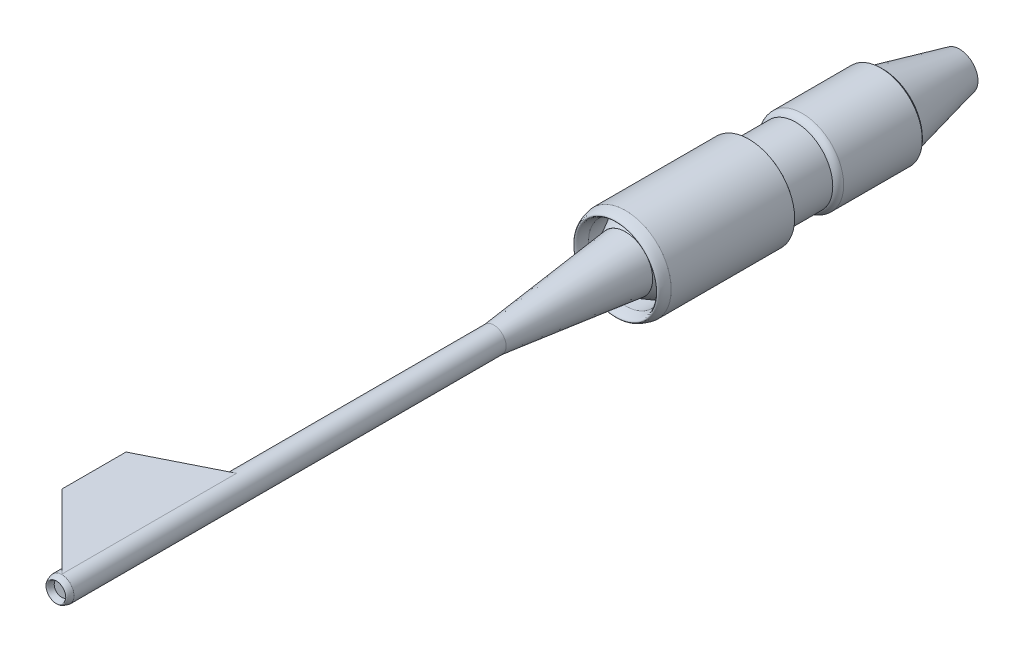
SolidWorks part; units mm, degrees
ref_plane "Front Plane" through (0, 0, 0) normal (0, 0, 1) x (1, 0, 0)
ref_plane "Top Plane" through (0, 0, 0) normal (0, 1, 0) x (1, 0, 0)
ref_plane "Right Plane" through (0, 0, 0) normal (1, 0, 0) x (0, 0, -1)
sketch "Sketch1" plane through (0, 0, 0) normal (0, 0, 1) x (1, 0, 0)
  circle A0 centre (0, 0) radius 416.25
  circle A1 centre (0, 0) radius 337.5
extrude "Boss-Extrude1" add sketch "Sketch1" against normal blind 1125
sketch "Sketch2" plane through (0, 0, 0) normal (1, 0, 0) x (0, 0, -1)
  line L0 (0, 416.25) -> (0, 337.5) construction
  line L1 (0, 337.5) -> (0, 376.875) construction
  line L2 (0, 376.875) -> (-90, 376.875) construction
  line L3 (0, 416.25) -> (0, 337.5)
  line L4 (0, 0) -> (98.8797, 0) construction
  spline S0 degree 2 poles (0, 337.5) (-180, 376.875) (0, 416.25) knots 0 0 0 1 1 1
revolve "Revolve1" add sketch "Sketch2" angle 360 about L4
ref_plane "Plane1" through (0, 0, 0) normal (0, 0, 1) x (1, 0, 0)
sketch "Sketch3" plane through (0, 0, 0) normal (0, 0, 1) x (1, 0, 0)
  circle A0 centre (0, 0) radius 247.5
sketch "Sketch4" plane through (0, 0, 0) normal (0, 1, 0) x (1, 0, 0)
  line L0 (0, 0) -> (0, -1200)
  line L1 (0, -1200) -> (112.5, -1200)
  line L2 (0, 0) -> (247.5, 0)
  line L3 (-247.5, 0) -> (247.5, 0) construction
  line L4 (-457.875, 0) -> (457.875, 0) construction
  line L5 (247.5, 0) -> (112.5, -1200)
revolve "Revolve2" add sketch "Sketch4" angle 360 about L0
sketch "Sketch5" plane through (0, 0, 1200) normal (0, 0, 1) x (1, 0, 0)
  circle A0 centre (0, 0) radius 112.5
extrude "Boss-Extrude2" add sketch "Sketch5" along normal blind 3937.5
sketch "Sketch14" plane through (0, 0, 0) normal (1, 0, 0) x (0, 0, -1)
  line L0 (-5137.5, 112.5) -> (-5137.5, 67.5)
  line L1 (-5137.5, 112.5) -> (-5137.5, -112.5) construction
  line L2 (-5137.5, 67.5) -> (-5137.5, 90)
  line L3 (-5137.5, 90) -> (-5187.5, 90) construction
  line L4 (-5137.5, 0) -> (-5198.2274, 0) construction
  line L5 (-5137.5, 112.5) -> (-5137.5, -112.5) construction
  spline S0 degree 2 poles (-5137.5, 67.5) (-5237.5, 90) (-5137.5, 112.5) knots 0 0 0 1 1 1
  dimension "D1" = 50
  dimension "D2" = 67.5
  dimension "D3" = 90
revolve "Revolve4" add sketch "Sketch14" angle 360 about L4 region at (0, 90, 5157.5)
sketch "Sketch15" plane through (0, 0, -1125) normal (0, 0, -1) x (-1, 0, 0)
  circle A0 centre (0, 0) radius 337.5
extrude "Boss-Extrude5" add sketch "Sketch15" along normal blind 486 separate body
sketch "Sketch16" plane through (0, 0, -1611) normal (0, 0, -1) x (-1, 0, 0)
  line L0 (0, 337.5) -> (0, 416.25) construction
  line L1 (0, 376.875) -> (79.8334, 376.875) construction
  circle A0 centre (0, 0) radius 337.5 construction
  circle A1 centre (0, 0) radius 337.5 construction
  circle A2 centre (0, 0) radius 416.25 construction
  circle A4 centre (0, 0) radius 376.875
extrude "Boss-Extrude6" add sketch "Sketch16" along normal blind 716
sketch "Sketch17" plane through (0, 0, 0) normal (1, 0, 0) x (0, 0, -1)
  line L0 (2327, 0) -> (3043, 0)
  line L1 (2327, -376.875) -> (2327, 376.875) construction
  line L2 (3043, 0) -> (3043, 168.75)
  line L3 (1611, 337.5) -> (2327, 337.5) construction
  line L4 (2327, 0) -> (2327, 337.5)
  line L5 (2327, 337.5) -> (3043, 168.75)
revolve "Revolve5" add sketch "Sketch17" angle 360 about L0
sketch "Sketch18" plane through (0, 0, 0) normal (1, 0, 0) x (0, 0, -1)
  line L0 (0, 247.5) -> (306.6324, 416.25)
  line L1 (1125, 416.25) -> (0, 416.25) construction
  line L2 (0, 247.5) -> (306.6324, 247.5)
  line L3 (306.6324, 247.5) -> (306.6324, 416.25)
  line L4 (0, 0) -> (306.6324, 0) construction
revolve "Revolve6" add sketch "Sketch18" angle 360 about L4
sketch "Sketch19" plane through (0, 0, 0) normal (1, 0, 0) x (0, 0, -1)
  line L1 (1611, 337.5) -> (1611, -337.5) construction
  line L2 (1611, 0) -> (1611, 337.5) construction
  line L3 (1611, 337.5) -> (1551, 337.5)
  line L4 (1611, 0) -> (1571, 0) construction
  line L5 (1611, 337.5) -> (1125, 337.5) construction
  line L6 (1611, 337.5) -> (1611, 376.875)
  line L7 (1611, 376.875) -> (1611, -376.875) construction
  arc A0 (1551, 337.5) -> (1611, 376.875) centre (1614.9642, 305.4325) cw
revolve "Revolve9" add sketch "Sketch19" angle 360 about L4
sketch "Sketch20" plane through (0, 0, 0) normal (1, 0, 0) x (0, 0, -1)
  line L0 (1125, 337.5) -> (1125, 416.25)
  line L1 (1125, 337.5) -> (1155, 337.5)
  line L2 (1551, 337.5) -> (1125, 337.5) construction
  line L3 (1125, 0) -> (1175, 0) construction
  line L4 (1125, -416.25) -> (1125, 416.25) construction
  conic Q0 (1155, 337.5) -> (1125, 416.25) control (1155, 382.5893) rho 0.44632
revolve "Revolve11" add sketch "Sketch20" angle 360 about L3
sketch "Sketch21" plane through (0, 0, 0) normal (1, 0, 0) x (0, 0, -1)
  line L0 (2327, 337.5) -> (2327, 376.875)
  line L1 (2327, 0) -> (2377, 0) construction
  line L2 (2327, -376.875) -> (2327, 376.875) construction
  line L3 (2327, 337.5) -> (2356.2, 330.618)
  line L4 (3043, 168.75) -> (2327, 337.5) construction
  conic Q0 (2327, 376.875) -> (2356.2, 330.618) control (2356.2, 357.1875) rho 0.453502
revolve "Revolve12" add sketch "Sketch21" angle 360 about L1
sketch3d "3DSketch1"
  line L0 (1.7689, 112.4861, 5137.5) -> (-673.2311, 112.4861, 5137.5) construction
  circle A0 centre (0, 0, 5137.5) radius 112.5 construction
  point P2 (0, 0, 5250)
ref_plane "Plane2" through (0, 112.4861, 0) normal (0, 1, 0) x (1, 0, 0)
sketch "Sketch22" plane through (0, 112.4861, 0) normal (0, 1, 0) x (1, 0, 0)
  line L0 (1.7689, -5137.5) -> (1.7689, -3540)
  line L1 (-673.2311, -5137.5) -> (-673.2311, -4462.5) construction
  line L2 (-673.2311, -4462.5) -> (1.7689, -4462.5) construction
  line L3 (-673.2311, -4462.5) -> (1.7689, -5137.5)
  line L4 (-673.2311, -4462.5) -> (-673.2311, -3877.5)
  line L5 (-673.2311, -3877.5) -> (1.7689, -3540)
extrude "Boss-Extrude7" add sketch "Sketch22" against normal blind 50
